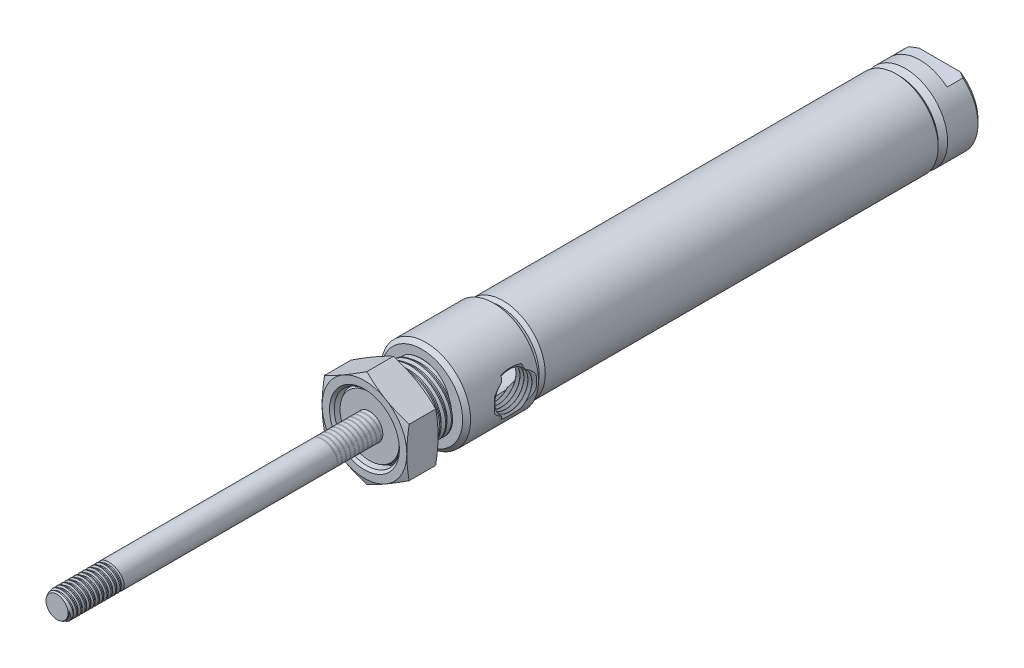
SolidWorks part; units mm, degrees
ref_plane "Front" through (0, 0, 0) normal (0, 0, 1) x (1, 0, 0)
ref_plane "Top" through (0, 0, 0) normal (0, 1, 0) x (1, 0, 0)
ref_plane "Right" through (0, 0, 0) normal (1, 0, 0) x (0, 0, -1)
sketch "Sketch1" plane through (0, 0, 0) normal (1, 0, 0) x (0, 0, -1)
  line L0 (-75.819, 0) -> (75.819, 0) construction
  line L1 (-63.119, -7.9375) -> (-63.119, 0) construction
  line L2 (-63.119, 7.9375) -> (-50.419, 7.9375) construction
  line L3 (-50.419, 0) -> (-50.419, 10.287)
  line L4 (-50.419, 10.287) -> (75.819, 10.287)
  line L5 (70.993, 10.287) -> (70.993, 7.874) construction
  line L6 (70.993, 7.874) -> (75.819, 7.874) construction
  line L7 (75.819, 10.287) -> (75.819, 0)
  line L8 (75.819, 0) -> (80.645, 0) construction
  line L9 (-63.119, -7.9375) -> (-50.419, -7.9375) construction
  line L10 (-50.419, -7.9375) -> (-50.419, -10.287) construction
  line L11 (-50.419, -10.287) -> (75.819, -10.287) construction
  line L12 (70.993, -10.287) -> (70.993, -7.874) construction
  line L13 (70.993, -7.874) -> (75.819, -7.874) construction
  line L18 (-63.119, 3.175) -> (-75.819, 3.175) construction
  line L19 (-75.819, 3.175) -> (-75.819, -3.175) construction
  line L20 (-75.819, -3.175) -> (-63.119, -3.175) construction
  line L25 (75.819, 0) -> (75.819, -10.287) construction
  line L26 (-63.119, 0) -> (-63.119, 7.9375) construction
  line L28 (-50.419, 0) -> (75.819, 0)
  line L29 (-56.769, 0) -> (-56.769, 7.9375) construction
  dimension "J Flat" = 15.748
  dimension "E OD" = 20.574
  dimension "K Flat Depth" = 4.826
  dimension "RM Pilot" = 15.875
  dimension "G Pilot Length" = 12.7
  dimension "Shaft Dia" = 6.35
  dimension "A Thread Length" = 12.7
  dimension "Total Length" = 151.638
revolve "Revolve1" add sketch "Sketch1" angle 360 about L8 reverse direction yes
sketch "Sketch2" plane through (0, 0, 0) normal (1, 0, 0) x (0, 0, -1)
  line L0 (-50.419, 10.287) -> (75.819, 10.287) construction
  line L1 (75.819, 10.287) -> (75.819, 0) construction
  line L2 (75.819, 0) -> (75.819, -10.287) construction
  line L3 (-50.419, -10.287) -> (75.819, -10.287) construction
  line L4 (70.993, -10.287) -> (70.993, -7.874) construction
  line L5 (70.993, -7.874) -> (75.819, -7.874) construction
  line L6 (70.993, 7.874) -> (75.819, 7.874) construction
  line L7 (70.993, 10.287) -> (70.993, 7.874) construction
  line L8 (70.993, 10.287) -> (75.819, 10.287)
  line L9 (75.819, 10.287) -> (75.819, 7.874)
  line L10 (75.819, -7.874) -> (75.819, -10.287)
  line L11 (70.993, -10.287) -> (75.819, -10.287)
  line L12 (70.993, -10.287) -> (70.993, -7.874)
  line L13 (70.993, -7.874) -> (75.819, -7.874)
  line L14 (70.993, 7.874) -> (75.819, 7.874)
  line L15 (70.993, 10.287) -> (70.993, 7.874)
extrude "Cut-Extrude1" cut sketch "Sketch2" against normal through all and the other way through all
chamfer "Chamfer1" distance 0.9652 angle 45 3 edges at (-10.287, 0, -75.819) (10.287, 0, -75.819) (-10.287, 0, 50.419)
sketch "Sketch4" plane through (0, 0, 0) normal (1, 0, 0) x (0, 0, -1)
  line L0 (-63.119, 0) -> (-63.119, 7.9375) construction
  line L1 (-75.819, 0) -> (75.819, 0) construction
  line L2 (-50.419, 0) -> (-50.419, 10.287) construction
  line L3 (-63.119, 7.9375) -> (-50.419, 7.9375) construction
  line L4 (-63.119, 0) -> (-63.119, 7.9375)
  line L5 (-63.119, 0) -> (-50.419, 0)
  line L6 (-50.419, 0) -> (-50.419, 7.9375)
  line L7 (-63.119, 7.9375) -> (-50.419, 7.9375)
  line L8 (-63.119, -7.9375) -> (-50.419, -7.9375) construction
  line L9 (-63.119, -7.9375) -> (-50.419, -7.9375) construction
revolve "Revolve2" add sketch "Sketch4" angle 360 about L5
sketch "Sketch5" plane through (0, 0, 0) normal (1, 0, 0) x (0, 0, -1)
  line L0 (-63.119, 7.9375) -> (-63.119, -7.9375) construction
  line L1 (-63.119, -7.9375) -> (-61.7079, -7.9375) construction
  line L2 (-61.7079, -7.9375) -> (-63.119, 7.9375) construction
  line L3 (-63.119, 7.9375) -> (-62.9433, 7.9531) construction
  line L4 (-62.9433, 7.9531) -> (-61.7134, 8.0624)
  line L5 (-61.7134, 8.0624) -> (-62.085, 7.2626)
  line L6 (-62.085, 7.2626) -> (-62.4364, 7.2314)
  line L7 (-62.4364, 7.2314) -> (-62.9433, 7.9531)
  line L8 (-62.3284, 8.0078) -> (-62.2607, 7.247) construction
  line L9 (-63.119, 7.9375) -> (-62.3221, 7.9375) construction
  line L10 (-62.3221, 7.9375) -> (-60.911, -7.9375) construction
  line L11 (-60.911, -7.9375) -> (-61.7079, -7.9375) construction
  line L12 (-63.119, 0) -> (-63.119, 7.9375) construction
  line L13 (-63.119, 7.9375) -> (-50.419, 7.9375) construction
  line L14 (-63.119, -7.9375) -> (-50.419, -7.9375) construction
  line L15 (-63.119, -0.1335) -> (-60.1141, 0.1335) construction
  point P19 (-61.6166, 0)
  dimension "D1" = 0.1764
  dimension "D2" = 0.3528
  dimension "Thread Pitch" = 1.4111
  dimension "D4" = 60
  dimension "D5" = 1.4111
revolve "Cut-Revolve2" cut sketch "Sketch5" angle 360 about L15
sketch "Sketch6" plane through (0, 0, 0) normal (1, 0, 0) x (0, 0, -1)
  line L0 (-63.119, 7.2314) -> (-61.896, 7.9375)
  line L1 (-61.896, 7.9375) -> (-63.119, 7.9375)
  line L2 (-63.119, 7.9375) -> (-63.119, 7.2314)
  line L3 (0, 0) -> (-63.119, 0) construction
  line L4 (-63.119, 0) -> (-63.119, 7.2314) construction
  line L5 (-63.119, 7.9375) -> (-50.419, 7.9375) construction
  line L6 (-63.119, 0) -> (-63.119, 7.9375) construction
  line L7 (-62.4364, 7.2314) -> (-63.119, 7.2314) construction
  dimension "D1" = 60
revolve "Cut-Revolve3" cut sketch "Sketch6" angle 360 about L3
pattern_linear "LPattern2" count 2 spacing 1.4111 along (0, 0, 1) count 9 spacing 1.4111 along (0, 0, -1) of "Cut-Revolve2"
combine bodies "Combine1" operation type add bodies to combine 113 109
sketch "Sketch7" plane through (0, 0, 0) normal (1, 0, 0) x (0, 0, -1)
  line L0 (-63.119, 3.2004) -> (-44.069, 3.2004)
  line L1 (-44.069, 3.2004) -> (-44.069, 6.3627)
  line L2 (-44.069, 9.525) -> (-17.907, 9.525) construction
  line L3 (-11.557, 9.525) -> (51.943, 9.525)
  line L4 (51.943, 0) -> (-63.119, 0)
  line L5 (-63.119, 0) -> (-63.119, 3.2004)
  line L6 (-63.119, 0) -> (-63.119, 7.9375) construction
  line L7 (-50.419, 0) -> (75.819, 0) construction
  line L8 (51.943, 0) -> (80.645, 0) construction
  line L9 (-50.419, 0) -> (-50.419, 10.287) construction
  line L10 (51.943, 9.525) -> (51.943, 0)
  line L11 (-63.119, 3.175) -> (-75.819, 3.175) construction
  line L12 (-44.069, 6.3627) -> (-17.907, 6.3627)
  line L13 (-17.907, 6.3627) -> (-17.907, 9.525)
  line L14 (-44.069, 6.3627) -> (-44.069, 9.525) construction
  line L15 (-17.907, 9.525) -> (-11.557, 9.525)
  line L16 (70.993, 7.874) -> (70.993, 10.287) construction
  dimension "D1" = 0.0254
  dimension "Bore Dia" = 19.05
  dimension "D2" = 6.35
  dimension "D3" = 19.05
  dimension "Stroke" = 63.5
  dimension "D4" = 6.35
revolve "Cut-Revolve5" cut sketch "Sketch7" angle 360 about L8
sketch "Sketch3" plane through (0, 0, 0) normal (1, 0, 0) x (0, 0, -1)
  line L0 (67.437, 10.287) -> (65.913, 8.763)
  line L1 (65.913, 8.763) -> (65.913, 9.525)
  line L2 (65.151, 10.287) -> (67.437, 10.287)
  line L3 (-31.369, 10.287) -> (-31.369, 9.525) construction
  line L4 (-31.369, 8.763) -> (-32.893, 10.287)
  line L5 (-32.893, 10.287) -> (-30.607, 10.287)
  line L6 (-50.419, 10.287) -> (75.819, 10.287) construction
  line L7 (-31.369, 8.763) -> (65.913, 8.763) construction
  line L8 (65.913, 9.525) -> (-31.369, 9.525) construction
  line L9 (-50.419, 0) -> (-50.419, 10.287) construction
  line L10 (70.993, 10.287) -> (70.993, 7.874) construction
  line L11 (75.819, 0) -> (80.645, 0) construction
  line L12 (75.819, 0) -> (80.645, 0) construction
  line L13 (65.913, 9.525) -> (65.151, 10.287)
  line L14 (65.913, 9.525) -> (65.913, 10.287) construction
  line L15 (-31.369, 9.525) -> (-30.607, 10.287)
  line L16 (-31.369, 9.525) -> (-31.369, 8.763)
  line L17 (-44.069, 9.525) -> (-17.907, 9.525) construction
  dimension "D1" = 19.05
  dimension "D2" = 5.08
  dimension "D4" = 45
revolve "Cut-Revolve1" cut sketch "Sketch3" angle 360 about L12
sketch "Sketch8" plane through (0, 0, 0) normal (1, 0, 0) x (0, 0, -1)
  line L0 (-63.119, 3.175) -> (-75.819, 3.175) construction
  line L1 (39.243, 3.175) -> (39.243, 9.4742)
  line L2 (39.243, 9.4742) -> (51.943, 9.4742)
  line L3 (51.943, 9.4742) -> (51.943, 0)
  line L4 (-75.819, 3.175) -> (-75.819, -3.175) construction
  line L5 (39.243, 3.175) -> (-75.819, 3.175)
  line L6 (-75.819, 3.175) -> (-75.819, 0)
  line L7 (51.943, 0) -> (-75.819, 0)
  line L8 (-75.819, 0) -> (75.819, 0) construction
  line L9 (-11.557, 9.525) -> (51.943, 9.525) construction
  line L11 (51.943, 9.525) -> (51.943, 0) construction
  dimension "D1" = 0.0508
  dimension "D2" = 12.7
revolve "Revolve3" add sketch "Sketch8" angle 360 about L7
sketch "Sketch10" plane through (0, 0, 0) normal (1, 0, 0) x (0, 0, -1)
  line L0 (-75.819, 3.175) -> (-75.819, -3.175) construction
  line L1 (-75.819, -3.175) -> (-74.7607, -3.175) construction
  line L2 (-74.7607, -3.175) -> (-75.819, 3.175) construction
  line L3 (-75.819, 3.175) -> (-75.6885, 3.1967) construction
  line L4 (-75.6885, 3.1967) -> (-74.7751, 3.349)
  line L5 (-74.7751, 3.349) -> (-75.0071, 2.7296)
  line L6 (-75.0071, 2.7296) -> (-75.2681, 2.6861)
  line L7 (-75.2681, 2.6861) -> (-75.6885, 3.1967)
  line L8 (-75.2318, 3.2729) -> (-75.1376, 2.7078) construction
  line L9 (-75.819, 3.175) -> (-75.2155, 3.175) construction
  line L10 (-75.2155, 3.175) -> (-74.1571, -3.175) construction
  line L11 (-74.1571, -3.175) -> (-74.7607, -3.175) construction
  line L12 (-75.819, 3.175) -> (-75.819, -3.175) construction
  line L13 (-63.119, 3.175) -> (-75.819, 3.175) construction
  line L14 (-75.819, -3.175) -> (-63.119, -3.175) construction
  line L15 (-75.819, -0.1888) -> (-73.5536, 0.1888) construction
  point P19 (-74.6863, 0)
  dimension "D1" = 0.1323
  dimension "D2" = 0.2646
  dimension "Shaft Thread Pitch" = 1.0583
  dimension "D4" = 1.0583
  dimension "D5" = 60
revolve "Cut-Revolve6" cut sketch "Sketch10" angle 360 about L15
sketch "Sketch11" plane through (0, 0, 0) normal (1, 0, 0) x (0, 0, -1)
  line L0 (-75.819, 3.175) -> (-74.9722, 3.175)
  line L1 (-74.9722, 3.175) -> (-75.819, 2.6861)
  line L2 (-75.819, 2.6861) -> (-75.819, 3.175)
  line L3 (0, 0) -> (-75.819, 0) construction
  line L4 (-75.819, 0) -> (-75.819, 2.6861) construction
  line L5 (-63.119, 3.175) -> (-75.819, 3.175) construction
  line L6 (-75.819, 3.175) -> (-75.819, -3.175) construction
  line L7 (-75.2681, 2.6861) -> (-75.819, 2.6861) construction
  dimension "D1" = 30
revolve "Cut-Revolve7" cut sketch "Sketch11" angle 360 about L3
pattern_linear "LPattern3" count 2 spacing 1.0583 along (0, 0, 1) count 12 spacing 1.0583 along (0, 0, -1) of "Cut-Revolve6"
pattern_linear "LPattern4" count 2 spacing 63.5 along (0, 0, 1) of bodies 122
sketch "Sketch118" plane through (0, 0, 0) normal (1, 0, 0) x (0, 0, -1)
  line L0 (-49.4538, 10.287) -> (-50.419, 9.3218) construction
  line L1 (-49.4538, 10.287) -> (-50.419, 9.3218)
  line L2 (-50.419, 10.287) -> (75.819, 10.287) construction
  line L3 (-49.4538, 10.287) -> (-32.893, 10.287)
  line L4 (-32.893, 10.287) -> (-32.893, 10.922)
  line L5 (-32.893, 10.922) -> (-49.4538, 10.922)
  line L6 (-49.4538, 10.922) -> (-50.419, 9.9568)
  line L7 (-50.419, 9.9568) -> (-50.419, 9.3218)
  line L8 (0, 0) -> (-32.893, 0) construction
  line L9 (-32.893, 0) -> (-32.893, 10.287) construction
  dimension "D1" = 21.844
revolve "Revolve4" add sketch "Sketch118" angle 360 about L8
ref_axis "Axis1" through (0, -21.7932, 0) along (0, 1, 0)
ref_plane "Plane1" through (0, 0, 0) normal (-1, 0, 0) x (0, 0, 1)
sketch "Sketch13" plane through (0, -1.7517, 219.4497) normal (1, 0, 0) x (0, 0, -1)
  line L0 (285.3119, 1.7517) -> (285.3119, 5.9543)
  line L1 (285.3119, 5.9543) -> (285.7566, 6.7833) construction
  line L2 (285.7566, 6.7833) -> (286.2522, 5.9837) construction
  line L3 (286.2522, 5.9837) -> (286.6969, 6.8127) construction
  line L4 (286.6969, 6.8127) -> (287.1925, 6.013) construction
  line L5 (286.2691, 6.0153) -> (286.6799, 6.781)
  line L6 (286.6799, 6.781) -> (286.7158, 6.7822)
  line L7 (286.7158, 6.7822) -> (287.1736, 6.0435)
  line L8 (287.1736, 6.0435) -> (287.2094, 6.0446)
  line L9 (285.3119, 5.9543) -> (287.1925, 6.013) construction
  line L10 (285.7566, 6.7833) -> (286.6969, 6.8127) construction
  line L11 (285.5342, 6.3688) -> (286.9447, 6.4128) construction
  line L12 (285.3119, 1.7517) -> (281.1093, 1.7517) construction
  line L13 (287.2094, 6.0446) -> (287.6202, 6.8104)
  line L14 (285.3289, 5.9859) -> (285.7396, 6.7517)
  line L15 (285.7396, 6.7517) -> (285.7755, 6.7528)
  line L16 (285.7755, 6.7528) -> (286.2333, 6.0141)
  line L17 (286.2333, 6.0141) -> (286.2691, 6.0153)
  line L18 (285.5342, 6.3688) -> (285.3119, 6.3618) construction
  line L19 (285.3119, 6.3618) -> (285.3119, 5.9543) construction
  line L20 (285.5342, -2.8653) -> (285.3119, -2.8584) construction
  line L21 (285.3289, 5.9859) -> (285.3119, 5.9543)
  line L22 (287.6202, 6.8104) -> (287.656, 6.8116)
  line L23 (287.656, 6.8116) -> (288.1138, 6.0729)
  line L24 (288.1138, 6.0729) -> (288.1497, 6.074)
  line L25 (288.1497, 6.074) -> (288.5605, 6.8398)
  line L26 (288.5605, 6.8398) -> (288.5963, 6.8409)
  line L27 (288.5963, 6.8409) -> (289.0541, 6.1023)
  line L28 (289.0541, 6.1023) -> (289.09, 6.1034)
  line L29 (289.09, 6.1034) -> (289.5008, 6.8692)
  line L30 (289.5008, 6.8692) -> (289.5366, 6.8703)
  line L31 (289.5366, 6.8703) -> (289.9944, 6.1317)
  line L32 (289.9944, 6.1317) -> (290.0303, 6.1328)
  line L33 (290.0303, 6.1328) -> (290.441, 6.8986)
  line L34 (290.441, 6.8986) -> (290.4769, 6.8997)
  line L35 (290.4769, 6.8997) -> (290.9347, 6.1611)
  line L36 (290.9347, 6.1611) -> (290.9705, 6.1622)
  line L37 (290.9705, 6.1622) -> (291.3813, 6.928)
  line L38 (291.3813, 6.928) -> (291.4172, 6.9291)
  line L39 (291.4172, 6.9291) -> (291.875, 6.1904)
  line L40 (291.875, 6.1904) -> (291.9108, 6.1916)
  line L41 (291.9108, 6.1916) -> (292.3216, 6.9574)
  line L42 (292.3216, 6.9574) -> (292.3575, 6.9585)
  line L43 (292.3575, 6.9585) -> (292.8153, 6.2198)
  line L44 (292.8153, 6.2198) -> (292.8511, 6.221)
  line L45 (292.8511, 6.221) -> (293.2619, 6.9867)
  line L46 (293.2619, 6.9867) -> (293.2977, 6.9879)
  line L47 (293.2977, 6.9879) -> (293.7555, 6.2492)
  line L48 (293.7555, 6.2492) -> (293.7914, 6.2503)
  line L49 (293.7914, 6.2503) -> (294.2022, 7.0161)
  line L50 (294.2022, 7.0161) -> (294.238, 7.0173)
  line L51 (294.238, 7.0173) -> (294.6958, 6.2786)
  line L52 (294.6958, 6.2786) -> (294.7317, 6.2797)
  line L53 (294.7317, 6.2797) -> (295.1425, 7.0455)
  line L54 (295.1425, 7.0455) -> (295.1783, 7.0466)
  line L55 (295.1783, 7.0466) -> (295.6361, 6.308)
  line L56 (295.6361, 6.308) -> (295.672, 6.3091)
  line L57 (295.672, 6.3091) -> (296.0827, 7.0749)
  line L58 (296.0827, 7.0749) -> (296.1186, 7.076)
  line L59 (296.1186, 7.076) -> (296.5764, 6.3374)
  line L60 (296.5764, 6.3374) -> (296.6122, 6.3385)
  line L61 (296.6122, 6.3385) -> (297.023, 7.1043)
  line L62 (297.023, 7.1043) -> (297.0589, 7.1054)
  line L63 (297.0589, 7.1054) -> (297.5167, 6.3668)
  line L64 (297.5167, 6.3668) -> (297.5525, 6.3679)
  line L65 (297.5525, 6.3679) -> (297.9633, 7.1337)
  line L66 (297.9633, 7.1337) -> (297.9991, 7.1348)
  line L67 (297.9991, 7.1348) -> (298.4569, 6.3961)
  line L68 (298.4569, 6.3961) -> (298.4928, 6.3973)
  line L69 (298.4928, 6.3973) -> (298.9036, 7.1631)
  line L70 (298.9036, 7.1631) -> (298.9394, 7.1642)
  line L71 (298.9394, 7.1642) -> (299.3972, 6.4255)
  line L72 (299.3972, 6.4255) -> (299.4331, 6.4267)
  line L73 (285.3119, 1.7517) -> (299.4331, 1.7517)
  line L74 (299.4331, 1.7517) -> (299.4331, 6.4267)
  line L75 (285.7576, 6.7522) -> (285.7566, 6.7833) construction
  line L76 (286.9447, 6.4128) -> (292.0175, 6.5714) construction
  line L77 (292.0175, 6.5714) -> (292.0175, 1.7517) construction
  line L78 (292.0175, 6.5714) -> (295.2687, 6.673) construction
  line L79 (295.2687, 6.673) -> (295.2687, 1.7517) construction
  line L82 (295.2687, 12.0387) -> (295.2687, 1.7517) construction
  line L84 (292.0175, 6.1949) -> (295.2687, 6.2965) construction
  dimension "D1" = 60
  dimension "D2" = 0.031
  dimension "E0" = 9.2202
  dimension "D3" = 0.0359
  dimension "Thread Pitch" = 0.9407
  dimension "Thread Taper" = 3.58
  dimension "L2 Thread Engagement" = 6.7056
  dimension "L4 Thread Length" = 9.9568
revolve "Cut-Revolve22" cut sketch "Sketch13" angle 360 about L12
sketch "Sketch52" plane through (0, 0, 0) normal (1, 0, 0) x (0, 0, -1)
  line L0 (65.8622, 0) -> (65.8622, 4.2025) construction
  line L1 (65.8622, 2.1013) -> (51.943, 2.1013)
  line L2 (65.8622, 2.1013) -> (65.8622, 0)
  line L3 (65.8622, 0) -> (51.943, 0)
  line L4 (51.943, 2.1013) -> (51.943, 0)
revolve "Cut-Revolve23" cut sketch "Sketch52" angle 360 about L3
ref_plane "Plane5" through (0, 0, 38.481) normal (0, 0, 1) x (1, 0, 0)
sketch "Sketch116" plane through (-125.5668, -1.3423, 38.481) normal (0, 0, 1) x (1, 0, 0)
  line L0 (126.532, 1.3423) -> (126.532, 5.5448)
  line L1 (126.532, 5.5448) -> (126.9767, 6.3738) construction
  line L2 (126.9767, 6.3738) -> (127.4723, 5.5742) construction
  line L3 (127.4723, 5.5742) -> (127.917, 6.4032) construction
  line L4 (127.917, 6.4032) -> (128.4126, 5.6036) construction
  line L5 (127.4893, 5.6058) -> (127.9001, 6.3716)
  line L6 (127.9001, 6.3716) -> (127.9359, 6.3727)
  line L7 (127.9359, 6.3727) -> (128.3937, 5.6341)
  line L8 (128.3937, 5.6341) -> (128.4296, 5.6352)
  line L9 (126.532, 5.5448) -> (128.4126, 5.6036) construction
  line L10 (126.9767, 6.3738) -> (127.917, 6.4032) construction
  line L11 (126.7544, 5.9593) -> (128.1648, 6.0034) construction
  line L12 (126.532, 1.3423) -> (122.3295, 1.3423) construction
  line L13 (128.4296, 5.6352) -> (128.8403, 6.401)
  line L14 (126.549, 5.5764) -> (126.9598, 6.3422)
  line L15 (126.9598, 6.3422) -> (126.9956, 6.3433)
  line L16 (126.9956, 6.3433) -> (127.4534, 5.6047)
  line L17 (127.4534, 5.6047) -> (127.4893, 5.6058)
  line L18 (126.7544, 5.9593) -> (126.532, 5.9524) construction
  line L19 (126.532, 5.9524) -> (126.532, 5.5448) construction
  line L20 (126.7544, -3.2748) -> (126.532, -3.2678) construction
  line L21 (126.549, 5.5764) -> (126.532, 5.5448)
  line L22 (128.8403, 6.401) -> (128.8762, 6.4021)
  line L23 (128.8762, 6.4021) -> (129.334, 5.6634)
  line L24 (129.334, 5.6634) -> (129.3698, 5.6646)
  line L25 (129.3698, 5.6646) -> (129.7806, 6.4304)
  line L26 (129.7806, 6.4304) -> (129.8165, 6.4315)
  line L27 (129.8165, 6.4315) -> (130.2743, 5.6928)
  line L28 (130.2743, 5.6928) -> (130.3101, 5.6939)
  line L29 (130.3101, 5.6939) -> (130.7209, 6.4597)
  line L30 (130.7209, 6.4597) -> (130.7568, 6.4609)
  line L31 (130.7568, 6.4609) -> (131.2146, 5.7222)
  line L32 (131.2146, 5.7222) -> (131.2504, 5.7233)
  line L33 (131.2504, 5.7233) -> (131.6612, 6.4891)
  line L34 (131.6612, 6.4891) -> (131.697, 6.4902)
  line L35 (131.697, 6.4902) -> (132.1548, 5.7516)
  line L36 (132.1548, 5.7516) -> (132.1907, 5.7527)
  line L37 (132.1907, 5.7527) -> (132.6015, 6.5185)
  line L38 (132.6015, 6.5185) -> (132.6373, 6.5196)
  line L39 (132.6373, 6.5196) -> (133.0951, 5.781)
  line L40 (133.0951, 5.781) -> (133.131, 5.7821)
  line L41 (133.131, 5.7821) -> (133.5418, 6.5479)
  line L42 (133.5418, 6.5479) -> (133.5776, 6.549)
  line L43 (133.5776, 6.549) -> (134.0354, 5.8104)
  line L44 (134.0354, 5.8104) -> (134.0713, 5.8115)
  line L45 (134.0713, 5.8115) -> (134.482, 6.5773)
  line L46 (134.482, 6.5773) -> (134.5179, 6.5784)
  line L47 (134.5179, 6.5784) -> (134.9757, 5.8398)
  line L48 (134.9757, 5.8398) -> (135.0115, 5.8409)
  line L49 (135.0115, 5.8409) -> (135.4223, 6.6067)
  line L50 (135.4223, 6.6067) -> (135.4582, 6.6078)
  line L51 (135.4582, 6.6078) -> (135.916, 5.8691)
  line L52 (135.916, 5.8691) -> (135.9518, 5.8703)
  line L53 (135.9518, 5.8703) -> (136.3626, 6.6361)
  line L54 (136.3626, 6.6361) -> (136.3984, 6.6372)
  line L55 (136.3984, 6.6372) -> (136.8562, 5.8985)
  line L56 (136.8562, 5.8985) -> (136.8921, 5.8996)
  line L57 (136.8921, 5.8996) -> (137.3029, 6.6654)
  line L58 (137.3029, 6.6654) -> (137.3387, 6.6666)
  line L59 (137.3387, 6.6666) -> (137.7965, 5.9279)
  line L60 (137.7965, 5.9279) -> (137.8324, 5.929)
  line L61 (137.8324, 5.929) -> (138.2432, 6.6948)
  line L62 (138.2432, 6.6948) -> (138.279, 6.6959)
  line L63 (138.279, 6.6959) -> (138.7368, 5.9573)
  line L64 (138.7368, 5.9573) -> (138.7727, 5.9584)
  line L65 (138.7727, 5.9584) -> (139.1834, 6.7242)
  line L66 (139.1834, 6.7242) -> (139.2193, 6.7253)
  line L67 (139.2193, 6.7253) -> (139.6771, 5.9867)
  line L68 (139.6771, 5.9867) -> (139.7129, 5.9878)
  line L69 (139.7129, 5.9878) -> (140.1237, 6.7536)
  line L70 (140.1237, 6.7536) -> (140.1596, 6.7547)
  line L71 (140.1596, 6.7547) -> (140.6174, 6.0161)
  line L72 (140.6174, 6.0161) -> (140.6532, 6.0172)
  line L73 (126.532, 1.3423) -> (140.6532, 1.3423)
  line L74 (140.6532, 1.3423) -> (140.6532, 6.0172)
  line L75 (126.9777, 6.3428) -> (126.9767, 6.3738) construction
  line L79 (136.4888, 6.2635) -> (136.4888, 1.3423) construction
  circle A1 centre (125.5668, 1.3423) radius 10.922 construction
  circle A2 centre (125.5668, 1.3423) radius 10.922 construction
  dimension "D1" = 60
  dimension "D2" = 0.031
  dimension "E0" = 9.2202
  dimension "D3" = 0.0359
  dimension "Thread Pitch" = 0.9407
  dimension "D4" = 3.58
  dimension "L4 Thread Length" = 9.9568
revolve "Cut-Revolve219" cut sketch "Sketch116" angle 360 about L12
ref_plane "Plane2" through (0, 0, 56.769) normal (0, 0, 1) x (1, 0, 0)
sketch "Sketch54" plane through (0, 0, 56.769) normal (0, 0, 1) x (1, 0, 0)
  line L1 (0, 11.9151) -> (-10.3188, 5.9575)
  line L2 (-10.3188, 5.9575) -> (-10.3188, -5.9575)
  line L3 (-10.3188, -5.9575) -> (0, -11.9151)
  line L4 (0, -11.9151) -> (10.3187, -5.9575)
  line L5 (10.3187, -5.9575) -> (10.3187, 5.9575)
  line L6 (10.3187, 5.9575) -> (0, 11.9151)
  circle A0 centre (0, 0) radius 10.3188 construction
  circle A1 centre (0, 0) radius 7.9375
  dimension "Nut Hex" = 20.6375
extrude "Extrude1" add sketch "Sketch54" along normal blind 7.62 separate body
sketch "Sketch55" plane through (0, 0, 0) normal (1, 0, 0) x (0, 0, -1)
  line L0 (-63.808, 11.9151) -> (-64.389, 11.9151)
  line L1 (-64.389, 11.9151) -> (-64.389, 10.3187)
  line L2 (-64.389, 10.3187) -> (-63.808, 11.9151)
  line L3 (-57.35, 11.9151) -> (-56.769, 11.9151)
  line L4 (-56.769, 11.9151) -> (-56.769, 10.3187)
  line L5 (-56.769, 10.3187) -> (-57.35, 11.9151)
  line L6 (-64.389, 10.3187) -> (-56.769, 10.3187) construction
  line L7 (-64.389, 11.9151) -> (-56.769, 11.9151) construction
  line L8 (-64.389, 5.9575) -> (-64.389, 11.9151) construction
  line L9 (-56.769, 5.9575) -> (-56.769, 11.9151) construction
  line L10 (0, 0) -> (-64.389, 0) construction
  line L11 (-64.389, 0) -> (-64.389, 10.3187) construction
  line L12 (-64.389, 8.5185) -> (-64.389, 7.9375)
  line L13 (-64.389, 7.9375) -> (-63.808, 7.9375)
  line L14 (-63.808, 7.9375) -> (-64.389, 8.5185)
  line L15 (-56.769, 8.5185) -> (-56.769, 7.9375)
  line L16 (-56.769, 7.9375) -> (-57.35, 7.9375)
  line L17 (-57.35, 7.9375) -> (-56.769, 8.5185)
  line L18 (-56.769, 7.9375) -> (-64.389, 7.9375) construction
  line L19 (-63.808, 11.9151) -> (-63.808, 7.9375) construction
  dimension "D1" = 20
  dimension "D2" = 20.6375
  dimension "D3" = 45
revolve "Cut-Revolve24" cut sketch "Sketch55" angle 360 about L10
equation "\"D1@Chamfer1\"=\"K Flat Depth@Sketch1\"/5"
equation "\"D1@Sketch5\"=\"Thread Pitch@Sketch5\"/8"
equation "\"D2@Sketch5\"=\"Thread Pitch@Sketch5\"/4"
equation "\"D5@Sketch5\"=\"Thread Pitch@Sketch5\""
equation "\"D3@LPattern2\"=\"Thread Pitch@Sketch5\""
equation "\"D4@LPattern2\"=\"Thread Pitch@Sketch5\""
equation "\"D2@LPattern2\"=\"G Pilot Length@Sketch1\"/\"Thread Pitch@Sketch5\""
equation "\"D1@Sketch10\"=\"Shaft Thread Pitch@Sketch10\"/8"
equation "\"D2@Sketch10\"=\"Shaft Thread Pitch@Sketch10\"/4"
equation "\"D4@Sketch10\"=\"Shaft Thread Pitch@Sketch10\""
equation "\"D3@LPattern3\"=\"Shaft Thread Pitch@Sketch10\""
equation "\"D4@LPattern3\"=\"Shaft Thread Pitch@Sketch10\""
equation "\"D2@LPattern3\"=\"A Thread Length@Sketch1\"/\"Shaft Thread Pitch@Sketch10\""
equation "\"D3@LPattern4\"=\"Stroke@Sketch7\""
equation "\"D2@Sketch13\"=\"Thread Pitch@Sketch13\"*.033"
equation "\"D2@Sketch55\"=\"Nut Hex@Sketch54\""
equation "\"D2@Sketch116\"=\"Thread Pitch@Sketch116\"*.033"
